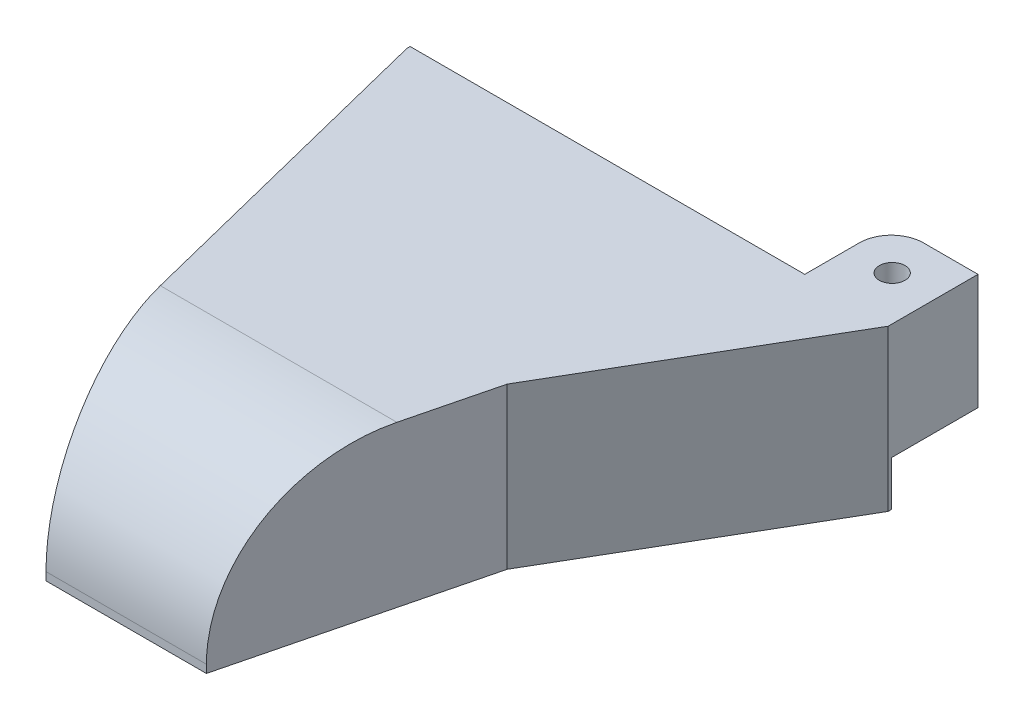
SolidWorks part; units mm, degrees
ref_plane "前视基准面" through (0, 0, 0) normal (0, 0, 1) x (1, 0, 0)
ref_plane "上视基准面" through (0, 0, 0) normal (0, 1, 0) x (1, 0, 0)
ref_plane "右视基准面" through (0, 0, 0) normal (1, 0, 0) x (0, 0, -1)
other "Configuration Table"
sketch "草图1" plane through (0, 0, 0) normal (0, 1, 0) x (1, 0, 0)
  line L1 (0, 0) -> (30, 0)
  line L2 (0, 0) -> (0, -6)
  line L3 (0, -6) -> (30, -6)
  line L4 (30, 0) -> (30, -6)
  dimension "D1" = 30
  dimension "D2" = 6
extrude "凸台-拉伸1" add sketch "草图1" along normal blind 2
sketch "草图2" plane through (0, 2, 0) normal (0, 1, 0) x (1, 0, 0)
  line L0 (30, -6) -> (30, 0) construction
  line L1 (30, 0) -> (0, 0) construction
  circle A0 centre (27.25, -3) radius 0.8
  dimension "D2" = 1.6
  dimension "D3" = 3
  dimension "D1" = 2.75
extrude "切除-拉伸1" cut sketch "草图2" against normal blind 2
sketch "草图3" plane through (0, 2, 0) normal (0, 1, 0) x (1, 0, 0)
  line L0 (0, 0) -> (0, -6) construction
  line L1 (0, -5.8) -> (1.6, -5.8)
  line L2 (0, -5.8) -> (0, -6)
  line L3 (0, -6) -> (1.6, -6)
  line L4 (1.6, -5.8) -> (1.6, -6)
  line L5 (0, -6) -> (30, -6) construction
  line L6 (30, 0) -> (0, 0) construction
  line L7 (30, -6) -> (30, 0) construction
  line L8 (23.4, -6) -> (25, -6)
  line L9 (23.4, -6) -> (23.4, -5.8)
  line L10 (23.4, -5.8) -> (25, -5.8)
  line L11 (25, -6) -> (25, -5.8)
  dimension "D1" = 1.6
  dimension "D2" = 5.8
  dimension "D3" = 5.8
  dimension "D4" = 1.6
  dimension "D5" = 5
extrude "凸台-拉伸2" add sketch "草图3" along normal blind 10
sketch "草图4" plane through (0, 12, 0) normal (0, 1, 0) x (1, 0, 0)
  line L1 (1.6, -5.8) -> (23.4, -5.8)
  line L2 (1.6, -5.8) -> (1.6, -6)
  line L3 (1.6, -6) -> (23.4, -6)
  line L4 (23.4, -5.8) -> (23.4, -6)
extrude "凸台-拉伸3" add sketch "草图4" against normal blind 1.6
sketch "草图5" plane through (0, 2, 0) normal (0, 1, 0) x (1, 0, 0)
  line L1 (25, -5.8) -> (30, -5.8)
  line L2 (25, -5.8) -> (25, -6)
  line L3 (25, -6) -> (30, -6)
  line L4 (30, -5.8) -> (30, -6)
extrude "凸台-拉伸4" add sketch "草图5" along normal blind 10
sketch "草图6" plane through (0, 0, 5.8) normal (0, 0, -1) x (-1, 0, 0)
  line L1 (-30, 12) -> (-24.6, 12)
  line L2 (-30, 12) -> (-30, 4.8)
  line L3 (-30, 4.8) -> (-24.6, 4.8)
  line L4 (-24.6, 12) -> (-24.6, 4.8)
  dimension "D1" = 5.4
  dimension "D2" = 7.2
extrude "凸台-拉伸5" add sketch "草图6" along normal blind 5.4
fillet "圆角1" radius 2 1 edges at (24.6, 8.4, 0.4)
sketch "草图7" plane through (0, 4.8, 0) normal (0, -1, 0) x (-1, 0, 0)
  circle A0 centre (-27.25, -3) radius 0.8
extrude "切除-拉伸2" cut sketch "草图7" against normal through all
sketch "草图8" plane through (0, 0, 0) normal (-1, 0, 0) x (0, 0, 1)
  line L1 (0, 2) -> (6, 2)
  line L2 (0, 2) -> (0, 0)
  line L3 (0, 0) -> (6, 0)
  line L4 (6, 2) -> (6, 0)
extrude "切除-拉伸3" cut sketch "草图8" against normal through all
sketch "草图9" plane through (0, 0, 6) normal (0, 0, 1) x (1, 0, 0)
  line L0 (23.4, 10.4) -> (23.4, 2) construction
  line L1 (1.6, 2) -> (23.4, 2)
  line L2 (1.6, 2) -> (1.6, 3.6)
  line L3 (1.6, 3.6) -> (23.4, 3.6)
  line L4 (23.4, 2) -> (23.4, 3.6)
  dimension "D1" = 1.6
extrude "凸台-拉伸7" add sketch "草图9" against normal up to surface (0.2 mm away) up to face at (15.92, 6.24, 5.8)
ref_plane "分割" through (0, 0, 6) normal (0, 0, 1) x (1, 0, 0)
sketch "草图11" plane through (0, 2, 0) normal (0, -1, 0) x (-1, 0, 0)
  line L0 (0, -6) -> (-7.5, -36)
  line L1 (-7.5, -36) -> (-17.5, -36)
  line L2 (-17.5, -36) -> (-25, -6)
  line L3 (0, -6) -> (-30, -6) construction
  line L4 (-25, -6) -> (0, -6)
  point P9 (-12.5, -36)
  point P10 (-12.5, -6)
  dimension "D1" = 1.6
  dimension "D2" = 0
  dimension "D3" = 30
  dimension "D4" = 10
extrude "凸台-拉伸9" add sketch "草图11" against normal blind 1.6
sketch "草图12" plane through (0, 3.6, 0) normal (0, 1, 0) x (1, 0, 0)
  line L11 (2.0492, -7.6) -> (8.7492, -34.4)
  line L12 (8.7492, -34.4) -> (16.2508, -34.4)
  line L13 (16.2508, -34.4) -> (22.9508, -7.6)
  line L16 (23.4, -5.8) -> (1.6, -5.8)
  line L17 (1.6, -5.8) -> (1.6, -6)
  line L18 (1.6, -6) -> (0, -6)
  line L19 (0, -6) -> (7.5, -36)
  line L20 (7.5, -36) -> (17.5, -36)
  line L21 (17.5, -36) -> (25, -6)
  line L22 (25, -6) -> (23.4, -6)
  line L23 (23.4, -6) -> (23.4, -5.8)
  line L26 (1.6, -6) -> (0, -6)
  line L27 (0, -6) -> (7.5, -36)
  line L28 (7.5, -36) -> (17.5, -36)
  line L29 (17.5, -36) -> (25, -6)
  line L30 (25, -6) -> (23.4, -6)
  line L32 (2.0492, -7.6) -> (1.6, -6)
  line L33 (22.9508, -7.6) -> (23.4, -6)
  line L35 (21.8, -7.4) -> (3.2, -7.4) construction
  line L36 (21.8, -7.6) -> (21.8, -7.4) construction
  line L37 (22.9508, -7.6) -> (21.8, -7.6) construction
  line L38 (23.4, -5.8) -> (1.6, -5.8) construction
  line L39 (23.4, -6) -> (23.4, -5.8) construction
  line L40 (3.2, -7.6) -> (2.0492, -7.6) construction
  line L41 (3.2, -7.4) -> (3.2, -7.6) construction
  line L42 (1.6, -5.8) -> (1.6, -6) construction
  dimension "D1" = 0
  dimension "D2" = 1.6
extrude "凸台-拉伸10" add sketch "草图12" along normal up to surface (8.4 mm away) up to face at (27.25, 12, 2.2)
sketch "草图13" plane through (0, 12, 0) normal (0, 1, 0) x (1, 0, 0)
  line L16 (1.6, -5.8) -> (1.6, -6)
  line L17 (1.6, -6) -> (2.0492, -7.6)
  line L18 (2.0492, -7.6) -> (8.7492, -34.4)
  line L19 (8.7492, -34.4) -> (16.2508, -34.4)
  line L20 (16.2508, -34.4) -> (22.9508, -7.6)
  line L21 (22.9508, -7.6) -> (23.4, -6)
  line L22 (23.4, -6) -> (23.4, -5.8)
  line L23 (23.4, -5.8) -> (1.6, -5.8)
  line L24 (1.6, -5.8) -> (1.6, -6)
  line L25 (1.6, -6) -> (2.0492, -7.6)
  line L26 (2.0492, -7.6) -> (8.7492, -34.4)
  line L27 (8.7492, -34.4) -> (16.2508, -34.4)
  line L28 (16.2508, -34.4) -> (22.9508, -7.6)
  line L29 (22.9508, -7.6) -> (23.4, -6)
  line L30 (23.4, -6) -> (23.4, -5.8)
  line L31 (23.4, -5.8) -> (1.6, -5.8)
  dimension "D1" = 0
extrude "凸台-拉伸11" add sketch "草图13" against normal blind 1.6
sketch "草图14" plane through (0, 12, 0) normal (0, 1, 0) x (1, 0, 0)
  line L0 (30, -6) -> (25, -6)
  line L1 (25, -6) -> (21.25, -21)
  line L2 (17.5, -36) -> (25, -6) construction
  line L3 (21.25, -21) -> (30, -6)
  dimension "D1" = 15
extrude "凸台-拉伸12" add sketch "草图14" against normal up to surface (10 mm away) up to face at (15.7143, 2, 14.5143)
sketch "草图15" plane through (0, 2, 0) normal (0, -1, 0) x (1, 0, 0)
  line L0 (8.7492, 34.4) -> (16.2508, 34.4)
  line L1 (16.2508, 34.4) -> (17.2508, 30.4)
  line L2 (17.2508, 30.4) -> (7.7492, 30.4)
  line L3 (7.7492, 30.4) -> (8.7492, 34.4)
  line L4 (17.5, 36) -> (7.5, 36) construction
  line L5 (7.5, 36) -> (0, 6) construction
  line L6 (21.25, 21) -> (17.5, 36) construction
  dimension "D1" = 1.6
  dimension "D2" = 180
  dimension "D3" = 180
  dimension "D4" = 1.6
  dimension "D5" = 1.6
  dimension "D6" = 4
extrude "切除-拉伸4" cut sketch "草图15" against normal blind 1.6
fillet "圆角2" radius 9 1 edges at (12.5, 10.4, 34.4)
fillet "圆角3" radius 9.5 1 edges at (12.5, 12, 36)
fillet "圆角4" radius 1 1 edges at (12.5, 3.6, 30.4)
